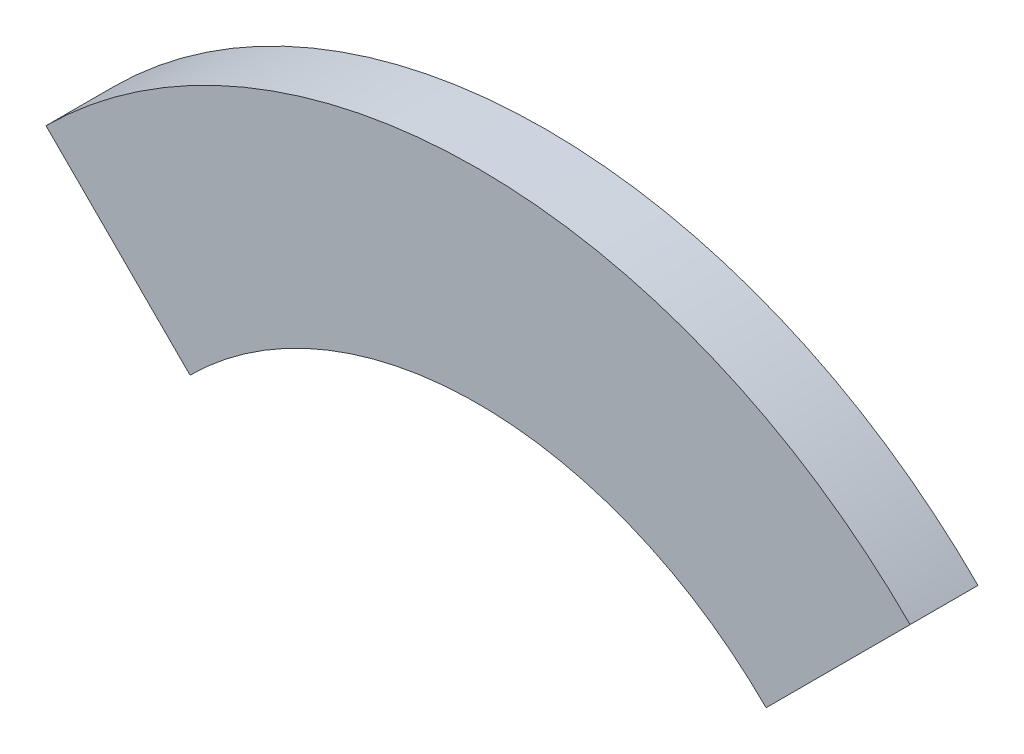
SolidWorks part; units mm, degrees
ref_plane "Front Plane" through (0, 0, 0) normal (0, 0, 1) x (1, 0, 0)
ref_plane "Top Plane" through (0, 0, 0) normal (0, 1, 0) x (1, 0, 0)
ref_plane "Right Plane" through (0, 0, 0) normal (1, 0, 0) x (0, 0, -1)
sketch "Sketch1" plane through (0, 0, 0) normal (0, 0, 1) x (1, 0, 0)
  line L0 (-127, 127) -> (0, 0) construction
  line L1 (0, 0) -> (127, 127) construction
  line L2 (0, 0) -> (-107.7631, 107.7631) construction
  line L3 (0, 0) -> (-161.6446, 161.6446) construction
  arc A0 (-127, 127) -> (127, 127) centre (0, 0) cw
  point P3 (0, 179.6051)
  dimension "D1" = 254
  dimension "D2" = 90
  dimension "D3" = 228.6
  dimension "D4" = 152.4
ref_plane "Plane1" through (0, 0, 0) normal (0, 0, 1) x (1, 0, 0)
ref_plane "Plane2" through (0, 0, 0) normal (-0.7071, -0.7071, 0) x (0.7071, -0.7071, 0)
sketch "Sketch2" plane through (0, 0, 0) normal (-0.7071, -0.7071, 0) x (0.7071, -0.7071, 0)
  line L0 (-179.6051, 0) -> (0, 0) construction
  line L1 (-228.6, 12.7) -> (-152.4, 12.7)
  line L2 (-228.6, 12.7) -> (-228.6, -12.7)
  line L3 (-228.6, -12.7) -> (-152.4, -12.7)
  line L4 (-152.4, 12.7) -> (-152.4, -12.7)
  line L7 (0, 0) -> (-179.6051, 0) construction
  point P0 (-179.6051, 0)
  point P9 (-152.4, 0)
  dimension "D3" = 25.4
sweep "Sweep1" add profiles "Sketch2" path "Sketch1"
ref_plane "Plane3" through (0, 127, 0) normal (0, -1, 0) x (-1, 0, 0)
sketch "Sketch3" plane through (0, 127, 0) normal (0, -1, 0) x (-1, 0, 0)
  line L0 (-127, 30.1437) -> (-127, -17.2956)
  line L1 (127, 30.1437) -> (127, -17.2956)
equation "\"theta\"= pi / 2 * 180 / pi"
equation "\"a\"= 6"
equation "\"b\"= 1"
equation "\"c\"= 9"
equation "\"D2@Sketch1\"=\"theta\""
equation "\"D3@Sketch2\"=\"b\""
equation "\"D3@Sketch1\"=\"c\""
equation "\"D4@Sketch1\"=\"a\""
equation "\"span\"= 10"
equation "\"D1@Sketch1\"=\"span\""
